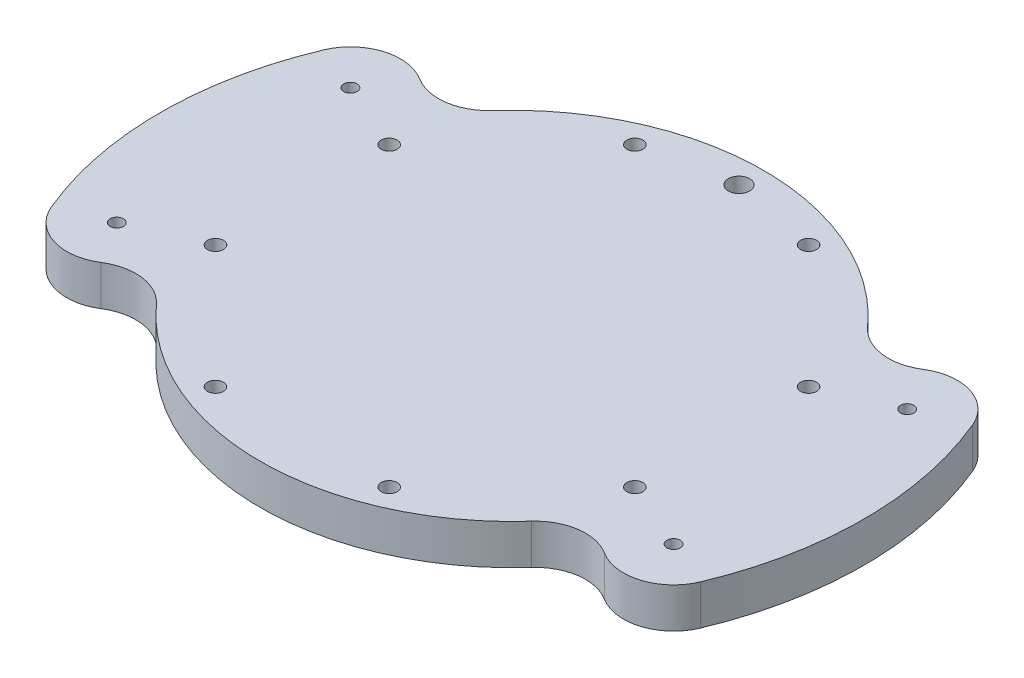
SolidWorks part; units mm, degrees
ref_plane "Front Plane" through (0, 0, 0) normal (0, 0, 1) x (1, 0, 0)
ref_plane "Top Plane" through (0, 0, 0) normal (0, 1, 0) x (1, 0, 0)
ref_plane "Right Plane" through (0, 0, 0) normal (1, 0, 0) x (0, 0, -1)
sketch "Sketch1" plane through (0, 0, 0) normal (0, 1, 0) x (1, 0, 0)
  line L0 (0, 42.5788) -> (0, -44.3324) construction
  line L1 (-13.0112, 31.4119) -> (0, 0) construction
  line L2 (41.7019, 17.5) -> (41.7019, -17.5) construction
  line L3 (31.8836, 20.1646) -> (44.561, 28.1823)
  line L4 (-64.518, 0) -> (71.4295, 0) construction
  line L5 (0, 0) -> (44.561, 28.1823) construction
  line L6 (31.8836, -20.1646) -> (44.561, -28.1823)
  line L7 (-31.8836, -20.1646) -> (-44.561, -28.1823)
  line L8 (-31.8836, 20.1646) -> (-44.561, 28.1823)
  circle A0 centre (0, 0) radius 37.725 construction
  circle A1 centre (-13.0112, 31.4119) radius 1
  circle A2 centre (13.0112, 31.4119) radius 1
  circle A3 centre (31.4119, 13.0112) radius 1
  circle A4 centre (31.4119, -13.0112) radius 1
  circle A5 centre (13.0112, -31.4119) radius 1
  circle A6 centre (-13.0112, -31.4119) radius 1
  circle A7 centre (-31.4119, -13.0112) radius 1
  circle A8 centre (-31.4119, 13.0112) radius 1
  circle A9 centre (41.7019, 17.5) radius 1
  circle A10 centre (41.7019, -17.5) radius 1
  circle A11 centre (0, 0) radius 52.725 construction
  arc A12 (44.561, 28.1823) -> (44.561, -28.1823) centre (0, 0) cw
  arc A13 (-31.8836, 20.1646) -> (31.8836, 20.1646) centre (0, 0) cw
  arc A14 (-31.8836, -20.1646) -> (31.8836, -20.1646) centre (0, 0) ccw
  circle A15 centre (-41.7019, 17.5) radius 1
  circle A16 centre (-41.7019, -17.5) radius 1
  arc A17 (-44.561, 28.1823) -> (-44.561, -28.1823) centre (0, 0) ccw
  point P23 (0, 0)
  point P27 (41.7019, 0)
  dimension "D1" = 75.45
  dimension "D3" = 2
  dimension "D6" = 15
  dimension "D9" = 2
  dimension "D2" = 34
  dimension "D4" = 22.5
  dimension "D7" = 45.225
  dimension "D8" = 35
  dimension "D10" = 7.5
  dimension "D5" = 8
extrude "Boss-Extrude1" add sketch "Sketch1" along normal blind 6
fillet "Fillet1" radius 7.5 8 edges at (44.561, 3, 28.1823) (31.8836, 3, 20.1646) (-44.561, 3, 28.1823) (-31.8836, 3, 20.1646) (44.561, 3, -28.1823) (31.8836, 3, -20.1646) (-44.561, 3, -28.1823) (-31.8836, 3, -20.1646)
sketch "Sketch2" plane through (0, 6, 0) normal (0, 1, 0) x (1, 0, 0)
  circle A0 centre (0, 34) radius 1.6
  dimension "D2" = 3.2
  dimension "D1" = 34
extrude "Cut-Extrude1" cut sketch "Sketch2" against normal through all
sketch "Sketch3" plane through (0, 6, 0) normal (0, 1, 0) x (1, 0, 0)
  arc A0 (28.0981, 25.1728) -> (-28.0981, 25.1728) centre (0, 0) ccw construction
  circle A1 centre (0, 0) radius 30.525
  dimension "D1" = 7.2
extrude "Cut-Extrude3" [suppressed] cut sketch "Sketch3" against normal blind 1.25 flip side to cut
hole_wizard "CSK for M2 Flat Head Machine Screw1" positions "Sketch9" profile "Sketch8" countersink size "M2" standard "ANSI Metric" end condition through all
sketch "Sketch9" plane through (0, 0, 0) normal (0, -1, 0) x (-1, 0, 0)
  point P0 (13.0112, -31.4119)
  point P3 (-13.0112, -31.4119)
  point P6 (-31.4119, -13.0112)
  point P9 (-31.4119, 13.0112)
  point P12 (-13.0112, 31.4119)
  point P15 (13.0112, 31.4119)
  point P18 (31.4119, 13.0112)
  point P21 (31.4119, -13.0112)
sketch "Sketch8" plane through (-13.0112, 0, 31.4119) normal (1, 0, 0) x (0, 0, -1)
  line L0 (0, 0) -> (0, 6)
  line L1 (0, 6) -> (1.2, 6)
  line L2 (1.2, 6) -> (1.2, 1)
  line L3 (1.2, 1) -> (2.2, 0)
  line L5 (2.2, 0) -> (0, 0)
  line L6 (-1.2, 1) -> (-2.2, 0) construction
  line L11 (0, -6.35) -> (0, 107.95) construction
  dimension "Thru Hole Dia." = 2.4
  dimension "Thru Hole Depth" = 6
  dimension "Near C'Sink Dia." = 4.4
  dimension "Near C'Sink Angle" = 90
equation "\"D7@Sketch1\"=\"D1@Sketch1\"/2+\"D6@Sketch1\"/2"
